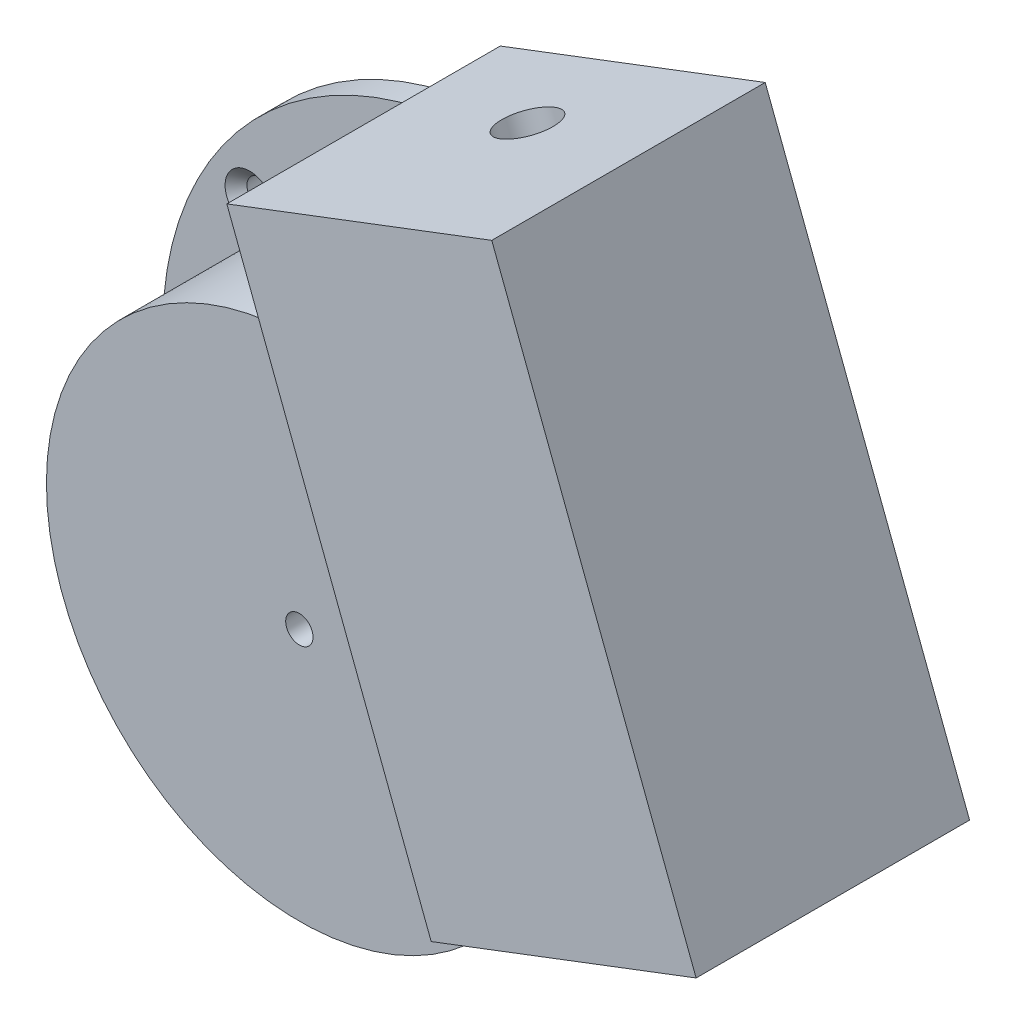
SolidWorks part; units mm, degrees
material "PET"
ref_plane "Piano frontale" through (0, 0, 0) normal (0, 0, 1) x (1, 0, 0)
ref_plane "Piano superiore" through (0, 0, 0) normal (0, 1, 0) x (1, 0, 0)
ref_plane "Piano destro" through (0, 0, 0) normal (1, 0, 0) x (0, 0, -1)
sketch "Schizzo1" plane through (0, 0, 0) normal (0, 0, 1) x (1, 0, 0)
  line L0 (0.3284, 23.9978) -> (-1.3054, 28.2879)
  line L1 (-1.3054, 28.2879) -> (18.0716, 35.6671)
  line L2 (18.0716, 35.6671) -> (33.0187, -3.5823)
  line L3 (33.0187, -3.5823) -> (22.8076, -7.471)
  line L6 (2.8947, 17.2589) -> (13.6417, -10.9615)
  arc A0 (2.8947, 17.2589) -> (13.6417, -10.9615) centre (0, 0) ccw
  arc A1 (0.3284, 23.9978) -> (22.8076, -7.471) centre (0, 0) ccw
  dimension "D1" = 35
  dimension "D2" = 48
extrude "Estrusione-Estrusione1" add sketch "Schizzo1" along normal blind 2
sketch "Schizzo3" plane through (0, 0, 2) normal (0, 0, 1) x (1, 0, 0)
  line L0 (13.6417, -10.9615) -> (15.3636, -10.3058)
  line L1 (22.8076, -7.471) -> (33.0187, -3.5823) construction
  line L2 (2.8947, 17.2589) -> (2.486, 18.3322)
  line L3 (-1.3054, 28.2879) -> (0.3284, 23.9978) construction
  arc A1 (2.486, 18.3322) -> (15.3636, -10.3058) centre (0, 0) ccw
  arc A2 (2.8947, 17.2589) -> (13.6417, -10.9615) centre (0, 0) ccw
  arc A3 (2.8947, 17.2589) -> (13.6417, -10.9615) centre (0, 0) ccw construction
  dimension "D1" = 37
extrude "Estrusione-Estrusione3" add sketch "Schizzo3" along normal blind 12
sketch "Schizzo5" plane through (0, 0, 2) normal (0, 0, 1) x (1, 0, 0)
  line L0 (2.8947, 17.2589) -> (8.6839, 7.6769)
  line L1 (8.6839, 7.6769) -> (1.2755, 27.1306)
  line L2 (1.2755, 27.1306) -> (16.9143, 33.0863)
  line L3 (16.9143, 33.0863) -> (30.4378, -2.4251)
  line L4 (30.4378, -2.4251) -> (12.9299, -9.0925)
  line L5 (13.6417, -10.9615) -> (12.9299, -9.0925)
  line L6 (13.6417, -10.9615) -> (33.0187, -3.5823)
  line L7 (33.0187, -3.5823) -> (18.0716, 35.6671)
  line L8 (18.0716, 35.6671) -> (-1.3054, 28.2879)
  line L9 (-1.3054, 28.2879) -> (2.8947, 17.2589)
  line L10 (13.6417, -10.9615) -> (2.8947, 17.2589) construction
  dimension "D1" = 2
  dimension "D2" = 2
  dimension "D3" = 2
  dimension "D4" = 2
extrude "Estrusione-Estrusione4" add sketch "Schizzo5" along normal blind 12
sketch "Schizzo7" plane through (0, 0, 2) normal (0, 0, 1) x (1, 0, 0)
  circle A0 centre (0, 0) radius 17.5
extrude "Taglio-Estrusione1" cut sketch "Schizzo7" against normal mid plane 24
sketch "Schizzo10" plane through (0, 0, 14) normal (0, 0, 1) x (1, 0, 0)
  line L0 (16.9143, 33.0863) -> (30.4378, -2.4251) construction
  line L1 (30.4378, -2.4251) -> (14.7989, -8.3807)
  line L2 (30.4378, -2.4251) -> (16.9143, 33.0863)
  line L3 (16.9143, 33.0863) -> (1.2755, 27.1306)
  line L4 (14.7989, -8.3807) -> (1.2755, 27.1306)
  line L5 (33.0187, -3.5823) -> (13.6417, -10.9615)
  line L6 (33.0187, -3.5823) -> (18.0716, 35.6671)
  line L7 (18.0716, 35.6671) -> (-1.3054, 28.2879)
  line L8 (13.6417, -10.9615) -> (-1.3054, 28.2879)
extrude "Estrusione-Estrusione5" add sketch "Schizzo10" along normal blind 4
sketch "Schizzo11" plane through (0, 0, 18) normal (0, 0, 1) x (1, 0, 0)
  line L0 (13.6417, -10.9615) -> (15.3636, -10.3058) construction
  line L1 (33.0187, -3.5823) -> (13.6417, -10.9615)
  line L2 (33.0187, -3.5823) -> (18.0716, 35.6671)
  line L3 (18.0716, 35.6671) -> (-1.3054, 28.2879)
  line L4 (13.6417, -10.9615) -> (-1.3054, 28.2879)
  arc A0 (2.8947, 17.2589) -> (13.6417, -10.9615) centre (0, 0) ccw construction
extrude "Estrusione-Estrusione6" add sketch "Schizzo11" along normal blind 2
sketch "Schizzo12" plane through (0, 0, 14) normal (0, 0, 1) x (1, 0, 0)
  circle A0 centre (0, 0) radius 18.5
extrude "Estrusione-Estrusione7" add sketch "Schizzo12" along normal blind 2
sketch "Schizzo13" plane through (0, 0, 16) normal (0, 0, 1) x (1, 0, 0)
  circle A0 centre (0, 0) radius 1
  dimension "D1" = 2
extrude "Taglio-Estrusione2" cut sketch "Schizzo13" against normal blind 2
sketch "Schizzo14" plane through (-9.5736, 25.1392, 0) normal (-0.3559, 0.9345, 0) x (0.9345, 0.3559, 0)
  line L0 (8.8474, -16) -> (8.8474, -18) construction
  line L1 (8.8474, -20) -> (8.8474, 0) construction
  line L2 (19.002, 0) -> (19.002, -7.5) construction
  line L4 (19.002, -7.5) -> (29.582, -7.5) construction
  line L5 (29.582, -20) -> (29.582, 0) construction
  line L7 (29.582, 0) -> (8.8474, 0) construction
  circle A1 centre (19.002, -7.5) radius 2
  dimension "D2" = 7.5
  dimension "D4" = 4
  dimension "D1" = 2
  dimension "D3" = 10.58
extrude "Taglio-Estrusione3" cut sketch "Schizzo14" against normal blind 41
sketch "Schizzo15" plane through (0, 0, 2) normal (0, 0, 1) x (1, 0, 0)
  line L0 (13.033, 20.1529) -> (-13.033, -20.1529) construction
  line L1 (-20.1529, 13.033) -> (20.1529, -13.033) construction
  line L2 (0, 0) -> (-0.8832, 23.9837) construction
  circle A0 centre (0, 0) radius 21
  arc A1 (0.3284, 23.9978) -> (22.8076, -7.471) centre (0, 0) ccw construction
  dimension "D3" = 35
  dimension "D1" = 42
  dimension "D2" = 24
  dimension "D6" = 24
hole_wizard "Foro svasato per Vite M1.6-1" positions "Schizzo3D1" profile "Schizzo16" countersink size "M1.6" standard "ISO" end condition through all
sketch3d "Schizzo3D1"
  line L0 (0, 0, 2) -> (-0.8832, 23.9837, 2) construction
  line L1 (-20.1529, 13.033, 2) -> (20.1529, -13.033, 2) construction
  line L2 (13.033, 20.1529, 2) -> (-13.033, -20.1529, 2) construction
  circle A0 centre (0, 0, 2) radius 21 construction
  point P0 (-0.7728, 20.9858, 2)
  point P6 (0, 0, 23)
  point P7 (-17.6338, 11.4039, 2)
  point P11 (-11.4039, -17.6338, 2)
  point P15 (17.6338, -11.4039, 2)
sketch "Schizzo16" plane through (-0.7728, 20.9858, 2) normal (1, 0, 0) x (0, -1, 0)
  line L0 (0, 0) -> (0, 2)
  line L1 (0, 2) -> (1, 2)
  line L2 (1, 2) -> (1, 0.8)
  line L3 (1, 0.8) -> (1.8, 0)
  line L5 (1.8, 0) -> (0, 0)
  line L6 (-1, 0.8) -> (-1.8, 0) construction
  line L11 (0, -6.35) -> (0, 107.95) construction
  dimension "Thru Hole Dia." = 2
  dimension "Thru Hole Depth" = 2
  dimension "Near C'Sink Dia." = 3.6
  dimension "Near C'Sink Angle" = 90
